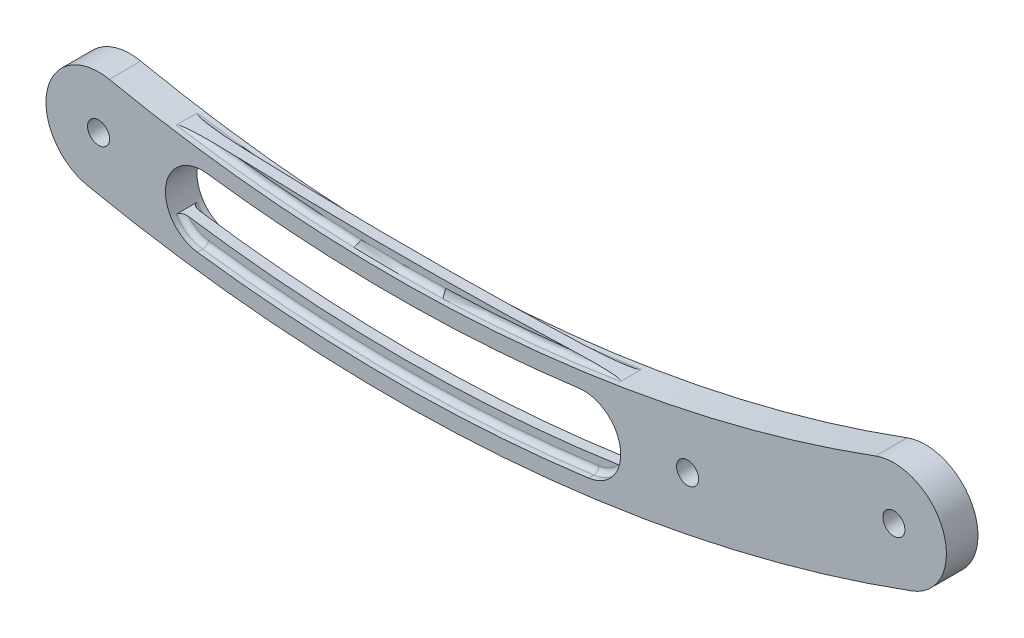
SolidWorks part; units mm, degrees
ref_plane "Alzado" through (0, 0, 0) normal (0, 0, 1) x (1, 0, 0)
ref_plane "Planta" through (0, 0, 0) normal (0, 1, 0) x (1, 0, 0)
ref_plane "Vista lateral" through (0, 0, 0) normal (1, 0, 0) x (0, 0, -1)
sketch "Croquis1" plane through (0, 0, 0) normal (0, 0, 1) x (1, 0, 0)
  line L0 (-112, 0) -> (0, 0) construction
  line L1 (0, 0) -> (39.2195, 11.246) construction
  arc A0 (-112, 0) -> (39.2195, 11.246) centre (-56, 269.3055) ccw construction
  arc A1 (-114.0359, -9.7906) -> (42.6812, 1.8643) centre (-56, 269.3055) ccw
  arc A2 (-109.9641, 9.7906) -> (35.7578, 20.6277) centre (-56, 269.3055) ccw
  arc A3 (-109.9641, 9.7906) -> (-114.0359, -9.7906) centre (-112, 0) ccw
  arc A4 (42.6812, 1.8643) -> (35.7578, 20.6277) centre (39.2195, 11.246) ccw
  circle A5 centre (0, 0) radius 2.1
  circle A6 centre (39.2195, 11.246) radius 2.1
  circle A7 centre (-112, 0) radius 2.1
  arc A8 (-92.2838, -3.3572) -> (-19.7162, -3.3572) centre (-56, 269.3055) ccw construction
  arc A9 (-93.2071, -10.296) -> (-18.7929, -10.296) centre (-56, 269.3055) ccw
  arc A10 (-91.3604, 3.5816) -> (-20.6396, 3.5816) centre (-56, 269.3055) ccw
  arc A11 (-91.3604, 3.5816) -> (-93.2071, -10.296) centre (-92.2838, -3.3572) ccw
  arc A12 (-18.7929, -10.296) -> (-20.6396, 3.5816) centre (-19.7162, -3.3572) ccw
  point P4 (-35.6, -5.0033)
  point P18 (-56, -5.7608)
  dimension "D4" = 20
  dimension "D5" = 4.2
  dimension "D6" = 4.2
  dimension "D7" = 4.2
  dimension "D9" = 20
  dimension "D10" = 3
  dimension "D1" = 16
  dimension "D2" = 40.8
  dimension "D3" = 112
  dimension "D8" = 20
extrude "Saliente-Extruir1" add sketch "Croquis1" along normal blind 6
ref_plane "Plano6" through (0, 0, 3) normal (0, 0, 1) x (1, 0, 0)
sketch "Croquis3" plane through (0, 0, 3) normal (0, 0, 1) x (1, 0, 0)
  arc A0 (-99.2226, -2.4338) -> (-12.7774, -2.4338) centre (-56, 269.3055) ccw construction
  arc A1 (-91.3604, 3.5816) -> (-93.2071, -10.296) centre (-92.2838, -3.3572) ccw construction
  arc A2 (-18.7929, -10.296) -> (-20.6396, 3.5816) centre (-19.7162, -3.3572) ccw construction
  arc A3 (-98.2286, -7.053) -> (-93.2071, -10.296) centre (-92.2838, -3.3572) ccw
  arc A4 (-93.2071, -10.296) -> (-18.7929, -10.296) centre (-56, 269.3055) ccw
  arc A5 (-93.2071, -10.296) -> (-18.7929, -10.296) centre (-56, 269.3055) ccw construction
  arc A6 (-98.2286, -7.053) -> (-13.7714, -7.053) centre (-56, 269.3055) ccw
  arc A7 (-13.7714, -7.053) -> (-18.7929, -10.296) centre (-19.7162, -3.3572) cw
  arc A8 (-98.2286, 7.6246) -> (-13.7714, 7.6246) centre (-56, 842.3166) ccw
  arc A9 (-98.2286, 7.6246) -> (-13.7714, 7.6246) centre (-56, 269.3055) ccw
  arc A10 (-109.9641, 9.7906) -> (35.7578, 20.6277) centre (-56, 269.3055) ccw construction
  point P22 (-71.1483, 17.6554)
  point P28 (-21.8204, 13.2619)
  point P29 (-98.2286, 8.7362)
  dimension "D1" = 2.5
extrude "Saliente-Extruir3" add sketch "Croquis3" along normal mid plane 2
fillet "Redondeo2" radius 1 8 edges at (-96.0814, -9.2375, 2) (-15.9186, -9.2375, 2) (-96.0814, -9.2375, 4) (-15.9186, -9.2375, 4) (-56, -12.7608, 2) (-56, -12.7608, 4) (-56, 4.2392, 2) (-56, 4.2392, 4)
